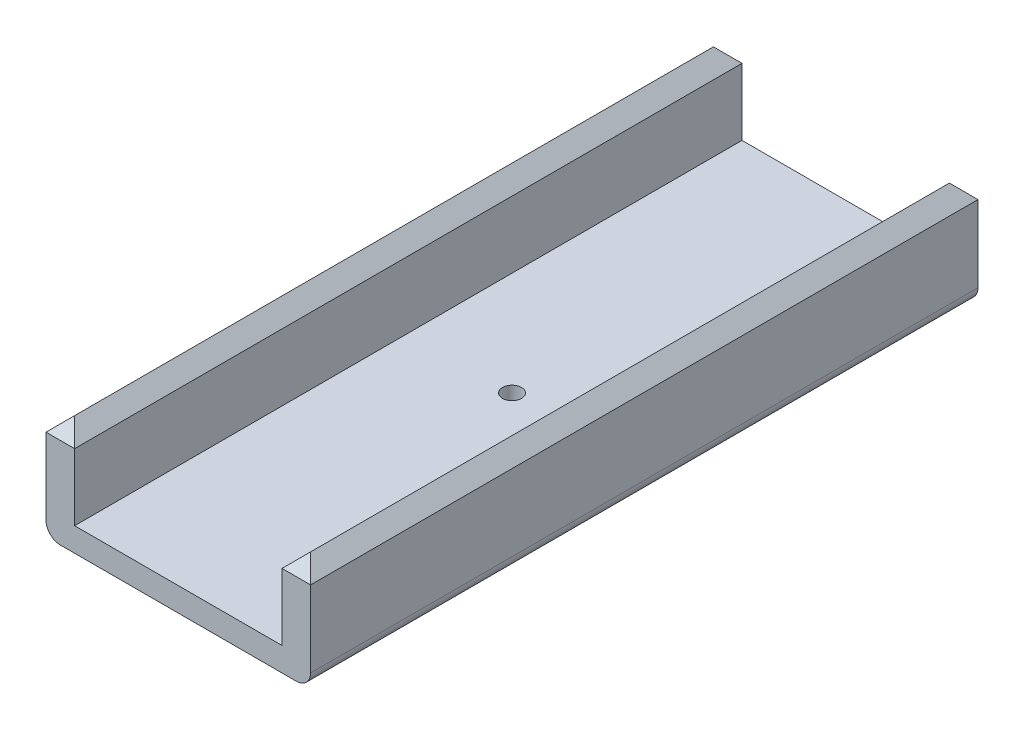
SolidWorks part; units mm, degrees
ref_plane "Front Plane" through (0, 0, 0) normal (0, 0, 1) x (1, 0, 0)
ref_plane "Top Plane" through (0, 0, 0) normal (0, 1, 0) x (1, 0, 0)
ref_plane "Right Plane" through (0, 0, 0) normal (1, 0, 0) x (0, 0, -1)
sketch "Sketch1" plane through (0, 0, 0) normal (0, 0, 1) x (1, 0, 0)
  line L1 (-27.75, -12.5) -> (27.75, -12.5)
  line L2 (-27.75, -12.5) -> (-27.75, 12.5)
  line L3 (-27.75, 12.5) -> (27.75, 12.5)
  line L4 (27.75, -12.5) -> (27.75, 12.5)
  line L5 (-27.75, -12.5) -> (27.75, 12.5) construction
  line L6 (-27.75, 12.5) -> (27.75, -12.5) construction
  point P0 (0, 0)
  dimension "D1" = 55.5
  dimension "D2" = 25
extrude "Boss-Extrude1" add sketch "Sketch1" along normal mid plane 140
sketch "Sketch2" plane through (0, 12.5, 0) normal (0, 1, 0) x (1, 0, 0)
  line L1 (-21.75, -75) -> (21.75, -75)
  line L2 (-21.75, -75) -> (-21.75, 75)
  line L3 (-21.75, 75) -> (21.75, 75)
  line L4 (21.75, -75) -> (21.75, 75)
  line L5 (-21.75, -75) -> (21.75, 75) construction
  line L6 (-21.75, 75) -> (21.75, -75) construction
  point P0 (0, 0)
  dimension "D1" = 43.5
  dimension "D2" = 150
extrude "Cut-Extrude1" cut sketch "Sketch2" against normal blind 20
sketch "Sketch3" plane through (0, -7.5, 0) normal (0, 1, 0) x (1, 0, 0)
  circle A0 centre (0, 0) radius 2
  dimension "D1" = 4
extrude "Cut-Extrude2" cut sketch "Sketch3" against normal through all
fillet "Fillet1" radius 3 2 edges at (27.75, -12.5, 0) (-27.75, -12.5, 0)
chamfer "Chamfer1" distance 6 angle 45 8 edges at (24.75, 12.5, -70) (27.75, 12.5, 0) (24.75, 12.5, 70) (21.75, 12.5, 0) (-24.75, 12.5, 70) (-27.75, 12.5, 0) (-24.75, 12.5, -70) (-21.75, 12.5, 0)
